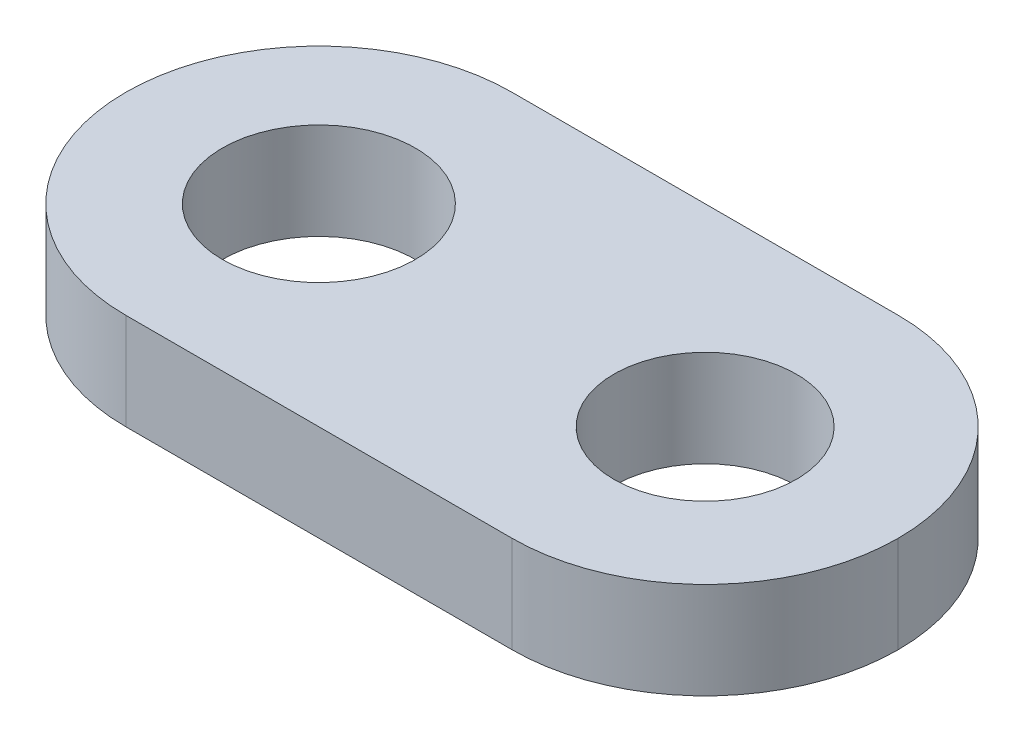
SolidWorks part; units mm, degrees
ref_plane "Front Plane" through (0, 0, 0) normal (0, 0, 1) x (1, 0, 0)
ref_plane "Top Plane" through (0, 0, 0) normal (0, 1, 0) x (1, 0, 0)
ref_plane "Right Plane" through (0, 0, 0) normal (1, 0, 0) x (0, 0, -1)
sketch "Sketch1" plane through (0, 0, 0) normal (0, 1, 0) x (1, 0, 0)
  line L0 (6.35, 6.35) -> (19.05, 6.35) construction
  line L1 (0, 0) -> (25.4, 0)
  line L2 (0, 0) -> (0, 12.7)
  line L3 (0, 12.7) -> (25.4, 12.7)
  line L4 (25.4, 0) -> (25.4, 12.7)
  circle A0 centre (19.05, 6.35) radius 3
  circle A1 centre (6.35, 6.35) radius 3.175
  dimension "D3" = 6
  dimension "D4" = 6.35
  dimension "D1" = 12.7
  dimension "D2" = 25.4
  dimension "D5" = 6.35
  dimension "D6" = 6.35
  dimension "D7" = 6.35
extrude "Boss-Extrude1" add sketch "Sketch1" along normal blind 3.175
fillet "Fillet1" radius 6.35 4 edges at (25.4, 1.5875, 0) (25.4, 1.5875, -12.7) (0, 1.5875, -12.7) (0, 1.5875, 0)
